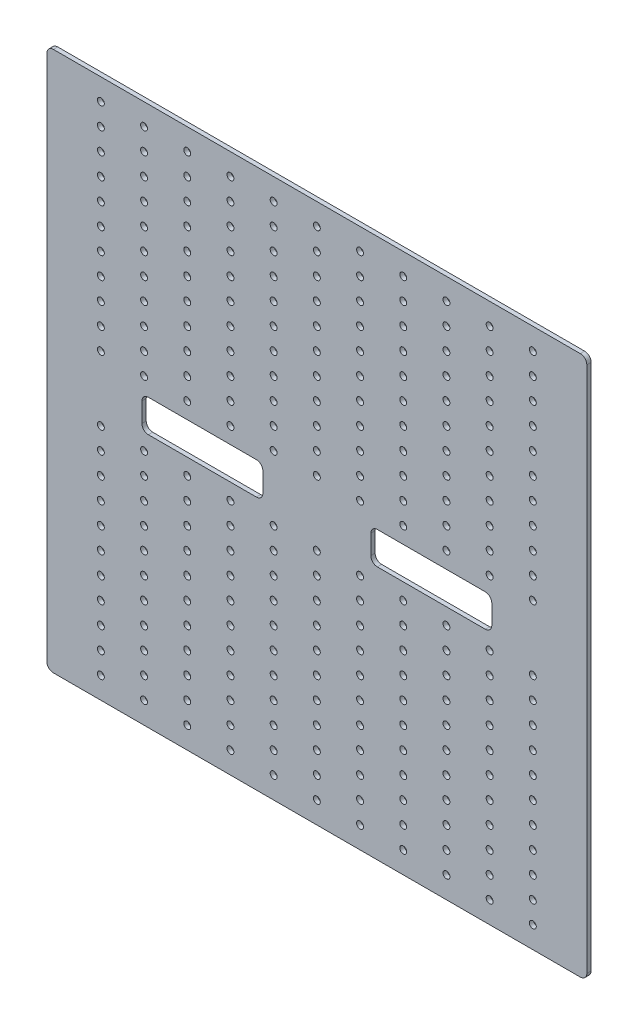
SolidWorks part; units mm, degrees
material "7050-T7651"
ref_plane "Front Plane" through (0, 0, 0) normal (0, 0, 1) x (1, 0, 0)
ref_plane "Top Plane" through (0, 0, 0) normal (0, 1, 0) x (1, 0, 0)
ref_plane "Right Plane" through (0, 0, 0) normal (1, 0, 0) x (0, 0, -1)
sketch "Sketch1" plane through (0, 0, 0) normal (0, 0, 1) x (1, 0, 0)
  line L0 (0, 0) -> (0, 250)
  line L1 (0, 250) -> (250, 250)
  line L2 (250, 250) -> (250, 0)
  line L3 (250, 0) -> (0, 0)
extrude "Boss-Extrude1" add sketch "Sketch1" along normal blind 2 contours L3 L0 L1 L2
fillet "Fillet1" radius 3 4 edges at (0, 0, 1) (250, 0, 1) (0, 250, 1) (250, 250, 1)
sketch "Sketch2" plane through (0, 0, 2) normal (0, 0, 1) x (1, 0, 0)
  line L0 (0, 0) -> (0, 125) construction
  line L1 (0, 3) -> (0, 247) construction
  line L2 (0, 0) -> (25, 0) construction
  line L4 (25, 0) -> (25, 250) construction
  line L5 (3, 250) -> (247, 250) construction
  line L7 (247, 0) -> (3, 0) construction
  line L8 (25, 250) -> (225, 250) construction
  line L9 (225, 250) -> (225, 0) construction
  line L10 (25, 250) -> (25, 240) construction
  line L11 (25, 240) -> (225, 240) construction
  line L12 (225, 240) -> (225, 140) construction
  line L13 (225, 140) -> (25, 140) construction
  line L14 (25, 140) -> (25, 110) construction
  line L15 (25, 110) -> (225, 110) construction
  line L16 (225, 110) -> (225, 10) construction
  line L17 (225, 10) -> (25, 10) construction
  line L18 (25, 10) -> (25, 0) construction
  circle A0 centre (25, 240) radius 1.6
  circle A1 centre (45, 240) radius 1.6
  circle A2 centre (65, 240) radius 1.6
  circle A3 centre (85, 240) radius 1.6
  circle A4 centre (105, 240) radius 1.6
  circle A5 centre (125, 240) radius 1.6
  circle A6 centre (145, 240) radius 1.6
  circle A7 centre (165, 240) radius 1.6
  circle A8 centre (185, 240) radius 1.6
  circle A9 centre (205, 240) radius 1.6
  circle A10 centre (225, 240) radius 1.6
  circle A11 centre (45, 230) radius 1.6
  circle A12 centre (65, 230) radius 1.6
  circle A13 centre (85, 230) radius 1.6
  circle A14 centre (105, 230) radius 1.6
  circle A15 centre (125, 230) radius 1.6
  circle A16 centre (145, 230) radius 1.6
  circle A17 centre (165, 230) radius 1.6
  circle A18 centre (185, 230) radius 1.6
  circle A19 centre (205, 230) radius 1.6
  circle A20 centre (225, 230) radius 1.6
  circle A21 centre (45, 220) radius 1.6
  circle A22 centre (65, 220) radius 1.6
  circle A23 centre (85, 220) radius 1.6
  circle A24 centre (105, 220) radius 1.6
  circle A25 centre (125, 220) radius 1.6
  circle A26 centre (145, 220) radius 1.6
  circle A27 centre (165, 220) radius 1.6
  circle A28 centre (185, 220) radius 1.6
  circle A29 centre (205, 220) radius 1.6
  circle A30 centre (225, 220) radius 1.6
  circle A31 centre (45, 210) radius 1.6
  circle A32 centre (65, 210) radius 1.6
  circle A33 centre (85, 210) radius 1.6
  circle A34 centre (105, 210) radius 1.6
  circle A35 centre (125, 210) radius 1.6
  circle A36 centre (145, 210) radius 1.6
  circle A37 centre (165, 210) radius 1.6
  circle A38 centre (185, 210) radius 1.6
  circle A39 centre (205, 210) radius 1.6
  circle A40 centre (225, 210) radius 1.6
  circle A41 centre (45, 200) radius 1.6
  circle A42 centre (65, 200) radius 1.6
  circle A43 centre (85, 200) radius 1.6
  circle A44 centre (105, 200) radius 1.6
  circle A45 centre (125, 200) radius 1.6
  circle A46 centre (145, 200) radius 1.6
  circle A47 centre (165, 200) radius 1.6
  circle A48 centre (185, 200) radius 1.6
  circle A49 centre (205, 200) radius 1.6
  circle A50 centre (225, 200) radius 1.6
  circle A51 centre (45, 190) radius 1.6
  circle A52 centre (65, 190) radius 1.6
  circle A53 centre (85, 190) radius 1.6
  circle A54 centre (105, 190) radius 1.6
  circle A55 centre (125, 190) radius 1.6
  circle A56 centre (145, 190) radius 1.6
  circle A57 centre (165, 190) radius 1.6
  circle A58 centre (185, 190) radius 1.6
  circle A59 centre (205, 190) radius 1.6
  circle A60 centre (225, 190) radius 1.6
  circle A61 centre (45, 180) radius 1.6
  circle A62 centre (65, 180) radius 1.6
  circle A63 centre (85, 180) radius 1.6
  circle A64 centre (105, 180) radius 1.6
  circle A65 centre (125, 180) radius 1.6
  circle A66 centre (145, 180) radius 1.6
  circle A67 centre (165, 180) radius 1.6
  circle A68 centre (185, 180) radius 1.6
  circle A69 centre (205, 180) radius 1.6
  circle A70 centre (225, 180) radius 1.6
  circle A71 centre (45, 170) radius 1.6
  circle A72 centre (65, 170) radius 1.6
  circle A73 centre (85, 170) radius 1.6
  circle A74 centre (105, 170) radius 1.6
  circle A75 centre (125, 170) radius 1.6
  circle A76 centre (145, 170) radius 1.6
  circle A77 centre (165, 170) radius 1.6
  circle A78 centre (185, 170) radius 1.6
  circle A79 centre (205, 170) radius 1.6
  circle A80 centre (225, 170) radius 1.6
  circle A81 centre (45, 160) radius 1.6
  circle A82 centre (65, 160) radius 1.6
  circle A83 centre (85, 160) radius 1.6
  circle A84 centre (105, 160) radius 1.6
  circle A85 centre (125, 160) radius 1.6
  circle A86 centre (145, 160) radius 1.6
  circle A87 centre (165, 160) radius 1.6
  circle A88 centre (185, 160) radius 1.6
  circle A89 centre (205, 160) radius 1.6
  circle A90 centre (225, 160) radius 1.6
  circle A91 centre (45, 150) radius 1.6
  circle A92 centre (65, 150) radius 1.6
  circle A93 centre (85, 150) radius 1.6
  circle A94 centre (105, 150) radius 1.6
  circle A95 centre (125, 150) radius 1.6
  circle A96 centre (145, 150) radius 1.6
  circle A97 centre (165, 150) radius 1.6
  circle A98 centre (185, 150) radius 1.6
  circle A99 centre (205, 150) radius 1.6
  circle A100 centre (225, 150) radius 1.6
  circle A101 centre (45, 140) radius 1.6
  circle A102 centre (65, 140) radius 1.6
  circle A103 centre (85, 140) radius 1.6
  circle A104 centre (105, 140) radius 1.6
  circle A105 centre (125, 140) radius 1.6
  circle A106 centre (145, 140) radius 1.6
  circle A107 centre (165, 140) radius 1.6
  circle A108 centre (185, 140) radius 1.6
  circle A109 centre (205, 140) radius 1.6
  circle A110 centre (225, 140) radius 1.6
  circle A111 centre (25, 230) radius 1.6
  circle A112 centre (25, 220) radius 1.6
  circle A113 centre (25, 210) radius 1.6
  circle A114 centre (25, 200) radius 1.6
  circle A115 centre (25, 190) radius 1.6
  circle A116 centre (25, 180) radius 1.6
  circle A117 centre (25, 170) radius 1.6
  circle A118 centre (25, 160) radius 1.6
  circle A119 centre (25, 150) radius 1.6
  circle A120 centre (25, 140) radius 1.6
  dimension "D1" = 11
  dimension "D2" = 11
extrude "Cut-Extrude1" cut sketch "Sketch2" against normal blind 2
sketch "Sketch3" plane through (0, 0, 2) normal (0, 0, 1) x (1, 0, 0)
  line L0 (0, 125) -> (250, 125) construction
  line L1 (0, 3) -> (0, 247) construction
  line L2 (250, 247) -> (250, 3) construction
ref_axis "Axis1" through (0, 125, 2) along (1, 0, 0)
ref_plane "Plane1" through (0, 125, 0) normal (0, -1, 0) x (1, 0, 0)
mirror "Mirror1" about plane through (0, 125, 0) normal (0, -1, 0) of "Cut-Extrude1"
sketch "Sketch5" plane through (0, 0, 2) normal (0, 0, 1) x (1, 0, 0)
  line L0 (0, 0) -> (0, 125) construction
  line L1 (0, 3) -> (0, 247) construction
  line L2 (0, 125) -> (250, 125) construction
  line L3 (250, 247) -> (250, 3) construction
  line L4 (125, 125) -> (125, 132.5) construction
  line L6 (150, 132.5) -> (206, 132.5) construction
  line L7 (206, 132.5) -> (206, 117.5) construction
  line L8 (206, 117.5) -> (150, 117.5) construction
  line L10 (150, 120.5) -> (150, 129.5)
  line L11 (153, 132.5) -> (203, 132.5)
  line L12 (206, 129.5) -> (206, 120.5)
  line L13 (203, 117.5) -> (153, 117.5)
  line L14 (44, 129.5) -> (44, 120.5)
  line L15 (97, 132.5) -> (47, 132.5)
  line L16 (100, 120.5) -> (100, 129.5)
  line L17 (47, 117.5) -> (97, 117.5)
  arc A0 (44, 129.5) -> (47, 132.5) centre (47, 129.5) cw
  arc A1 (44, 120.5) -> (47, 117.5) centre (47, 120.5) ccw
  arc A2 (100, 120.5) -> (97, 117.5) centre (97, 120.5) cw
  arc A3 (97, 132.5) -> (100, 129.5) centre (97, 129.5) cw
  arc A4 (150, 129.5) -> (153, 132.5) centre (153, 129.5) cw
  arc A5 (150, 120.5) -> (153, 117.5) centre (153, 120.5) ccw
  arc A6 (206, 120.5) -> (203, 117.5) centre (203, 120.5) cw
  arc A7 (203, 132.5) -> (206, 129.5) centre (203, 129.5) cw
  point P15 (125, 128.75)
  point P21 (44, 132.5)
  point P24 (44, 117.5)
  point P27 (100, 117.5)
  point P30 (100, 132.5)
  dimension "D1" = 3
  dimension "D2" = 25
  dimension "D3" = 50
extrude "Cut-Extrude2" cut sketch "Sketch5" against normal blind 2
